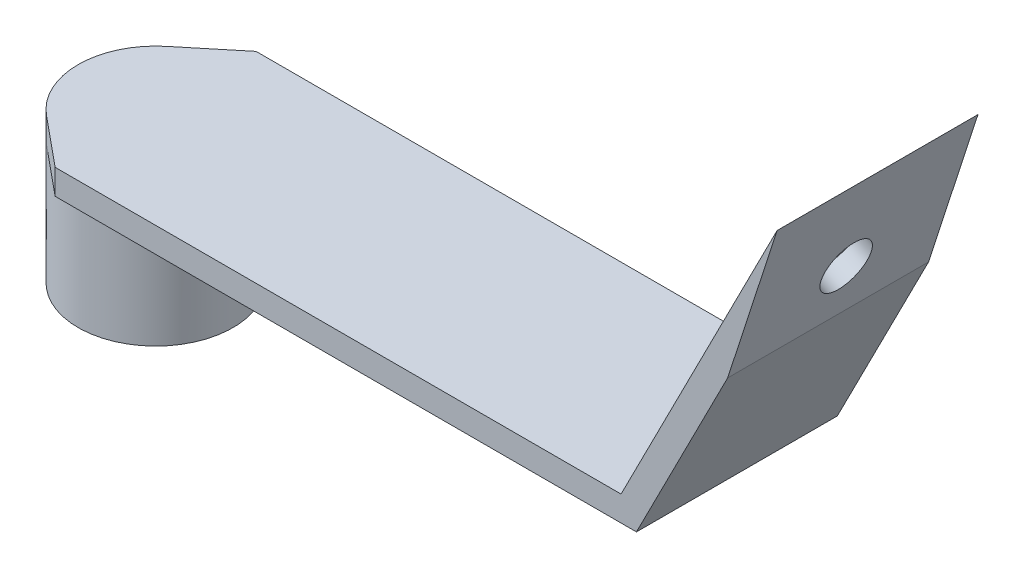
SolidWorks part; units mm, degrees
ref_plane "Front" through (0, 0, 0) normal (0, 0, 1) x (1, 0, 0)
ref_plane "Top" through (0, 0, 0) normal (0, 1, 0) x (1, 0, 0)
ref_plane "Right" through (0, 0, 0) normal (1, 0, 0) x (0, 0, -1)
sketch "Sketch1" plane through (0, 0, 0) normal (0, 0, 1) x (1, 0, 0)
  line L0 (-92.4958, -3.4222) -> (-20.9415, -3.4222)
  line L1 (-20.9415, -3.4222) -> (-1.2089, 35.3052)
  line L3 (-92.4958, -6.5972) -> (-18.9958, -6.5972)
  line L6 (-92.4958, -3.4222) -> (-92.4958, -6.5972)
  line L8 (-7.4645, 16.0344) -> (-1.2089, 35.3052)
  line L9 (-1.2089, 35.3052) -> (23.8053, 30.1317) construction
  line L10 (0.5203, 31.7054) -> (23.1623, 27.0225) construction
  line L11 (-18.9958, -6.5972) -> (-7.4645, 16.0344)
  line L12 (-18.9958, -6.5972) -> (0.5203, 31.7054) construction
  dimension "D2" = 73.5
  dimension "D3" = 25.4
  dimension "D4" = 117
  dimension "D1" = 3.175
extrude "Boss-Extrude1" add sketch "Sketch1" along normal blind 25.4
sketch "Sketch2" plane through (0, -3.4222, 0) normal (0, 1, 0) x (1, 0, 0)
  line L0 (-92.4958, -25.4) -> (-92.4958, 0) construction
  circle A0 centre (-92.4958, -12.7) radius 7.0714
  circle A1 centre (-92.4958, -12.7) radius 9.8014
extrude "Boss-Extrude2" add sketch "Sketch2" against normal blind 19
sketch "Sketch3" plane through (0, -3.4222, 0) normal (0, 1, 0) x (1, 0, 0)
  line L0 (-92.4958, 0) -> (-98.7286, -5.1356)
  line L1 (-98.7286, -5.1356) -> (-98.7286, -20.2644)
  line L2 (-98.7286, -20.2644) -> (-92.4958, -25.4)
  line L3 (-92.4958, 0) -> (-92.4958, -25.4)
  line L4 (-98.7286, -5.1356) -> (-102.2973, -12.7)
  line L5 (-102.2973, -12.7) -> (-98.7286, -20.2644)
  arc A0 (-92.4958, -2.8986) -> (-92.4958, -22.5014) centre (-92.4958, -12.7) ccw construction
  line M1 (-92.4958, 0) -> (-92.4958, -2.8986)
  arc M2 (-92.4958, -2.8986) -> (-92.4958, -22.5014) centre (-92.4958, -12.7) ccw
  line M3 (-92.4958, -22.5014) -> (-92.4958, -25.4)
  arc M7 (-92.4958, -19.7714) -> (-92.4958, -5.6286) centre (-92.4958, -12.7) cw
  line M8 (-92.4958, -5.6286) -> (-92.4958, -19.7714)
extrude "Boss-Extrude3" add sketch "Sketch3" against normal blind 3.175 contours L1 M7 | L4 L5 L1 M7 | L3 L1 M7 M2 | L2 M2 M3 | L1 M7 M8 | L3 L1 M2 M7 | L0 M1 M2 region at (-94.1319, -3.4222, 2.2347) region at (-95.8201, -3.4222, 5.2602) region at (-100.057, -3.4222, 12.7) region at (-95.3165, -3.4222, 12.7) region at (-99.0658, -3.4222, 12.7) region at (-95.8201, -3.4222, 20.1398) region at (-94.1319, -3.4222, 23.1653)
sketch "Sketch4" plane through (-15.241, 7.7657, 0) normal (-0.891, 0.454, 0) x (0, 0, 1)
  line L0 (25.4, 30.9084) -> (25.4, -12.5564) construction
  line L1 (25.4, 30.9084) -> (0, 30.9084) construction
  circle A0 centre (12.7, 18.2084) radius 3.175
  dimension "D1" = 6.35
  dimension "D2" = 12.7
  dimension "D3" = 12.7
extrude "Cut-Extrude1" cut sketch "Sketch4" against normal blind 3.175
